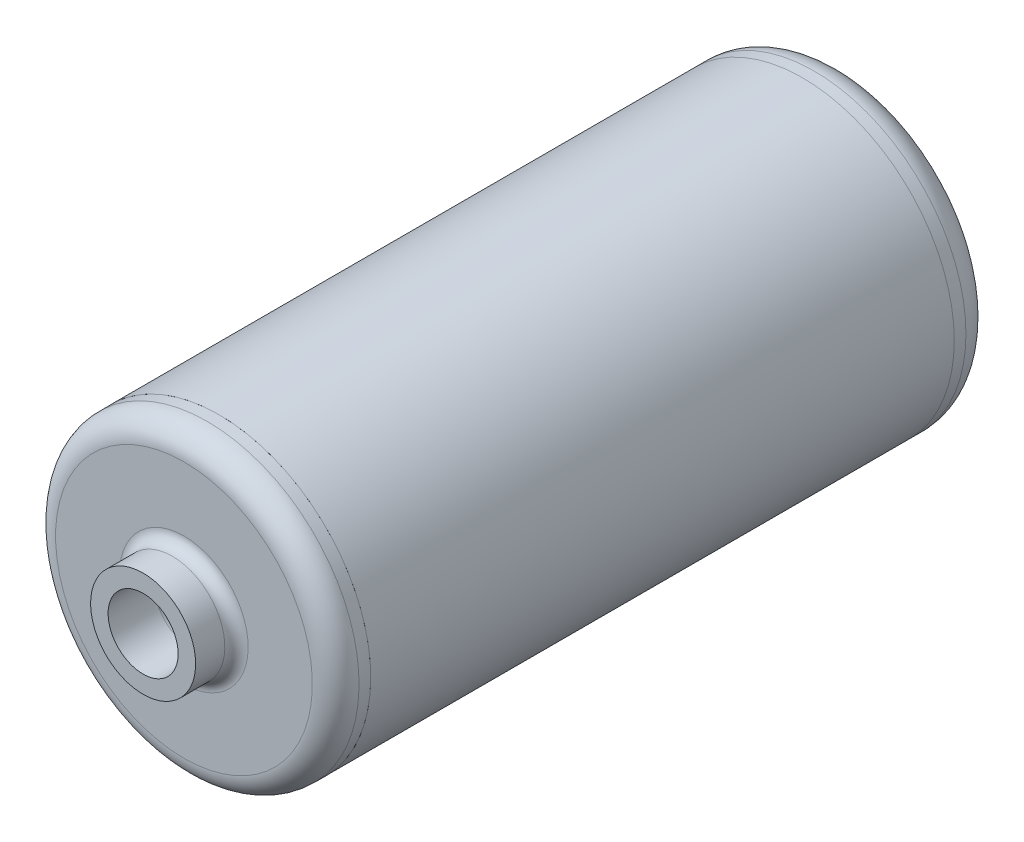
SolidWorks part; units mm, degrees
ref_plane "Alzado" through (0, 0, 0) normal (0, 0, 1) x (1, 0, 0)
ref_plane "Planta" through (0, 0, 0) normal (0, 1, 0) x (1, 0, 0)
ref_plane "Vista lateral" through (0, 0, 0) normal (1, 0, 0) x (0, 0, -1)
sketch "Croquis1" plane through (0, 0, 0) normal (0, 0, 1) x (1, 0, 0)
  circle A0 centre (0, 0) radius 26
  circle A1 centre (0, 0) radius 22
  dimension "D1" = 52
  dimension "D2" = 4
extrude "Saliente-Extruir1" add sketch "Croquis1" along normal blind 50 and the other way blind 50
ref_plane "Plano1" through (0, 0, 0) normal (1, 0, 0) x (0, 0, -1)
sketch "Croquis2" plane through (0, 0, 0) normal (1, 0, 0) x (0, 0, -1)
  line L0 (65.9873, 0) -> (-65.9873, 0) construction
  line L3 (-50, 26) -> (-50, -26) construction
  line L4 (-50, 26) -> (-50, -26) construction
  line L5 (50, -22) -> (50, 22) construction
  line L6 (50, -22) -> (50, 22) construction
  line L7 (-50, 22) -> (-50, -22) construction
  line L8 (-50, 22) -> (-50, -22) construction
  line L9 (-50, 22) -> (-43, 22)
  line L10 (-43, 22) -> (-43, 21)
  line L11 (-45, 19) -> (-49, 19)
  line L12 (-53, 15) -> (-53, 8)
  line L13 (-55, 6) -> (-63, 6)
  line L14 (-63, 6) -> (-63, 9)
  line L15 (-63, 9) -> (-58, 9)
  line L16 (-56, 11) -> (-56, 22)
  line L17 (-52, 26) -> (-50, 26)
  line L18 (-50, 26) -> (-50, 22)
  arc A0 (-56, 22) -> (-52, 26) centre (-52, 22) cw
  arc A1 (-49, 19) -> (-53, 15) centre (-49, 15) ccw
  arc A2 (-43, 21) -> (-45, 19) centre (-45, 21) cw
  arc A3 (-58, 9) -> (-56, 11) centre (-58, 11) ccw
  arc A4 (-53, 8) -> (-55, 6) centre (-55, 8) cw
  point P4 (0, 0)
  dimension "D8" = 4
  dimension "D9" = 2
  dimension "D1" = 6
  dimension "D2" = 3
  dimension "D3" = 3
  dimension "D4" = 3
  dimension "D5" = 10
  dimension "D6" = 3
  dimension "D7" = 10
revolve "Revolución2" add sketch "Croquis2" angle 360 about L0
sketch "Croquis3" plane through (0, 0, 0) normal (1, 0, 0) x (0, 0, -1)
  line L0 (0, 0) -> (78.2121, 0) construction
  line L1 (50, -22) -> (50, 22) construction
  line L2 (50, -22) -> (50, 22) construction
  line L3 (50, -26) -> (50, 26) construction
  line L4 (50, -26) -> (50, 26) construction
  line L5 (45, 22) -> (50, 22)
  line L6 (57, -26) -> (43, -26) construction
  line L7 (57, -26) -> (57, 26) construction
  line L8 (57, 26) -> (43, 26) construction
  line L9 (43, -26) -> (43, 26) construction
  line L10 (57, -26) -> (43, 26) construction
  line L11 (57, 26) -> (43, -26) construction
  line L12 (50, 22) -> (50, 26)
  line L13 (50, 26) -> (52, 26)
  line L14 (57, 21) -> (57, 8)
  line L15 (55, 6) -> (45, 6)
  line L16 (43, 8) -> (43, 20)
  arc A0 (52, 26) -> (57, 21) centre (52, 21) cw
  arc A1 (57, 8) -> (55, 6) centre (55, 8) cw
  arc A2 (45, 6) -> (43, 8) centre (45, 8) cw
  arc A3 (45, 22) -> (43, 20) centre (45, 20) ccw
  point P7 (50, 0)
  point P20 (57, 6)
  point P23 (43, 6)
  point P26 (43, 22)
  dimension "D3" = 5
  dimension "D4" = 2
  dimension "D1" = 14
  dimension "D2" = 6
revolve "Revolución3" add sketch "Croquis3" angle 360 about L0
